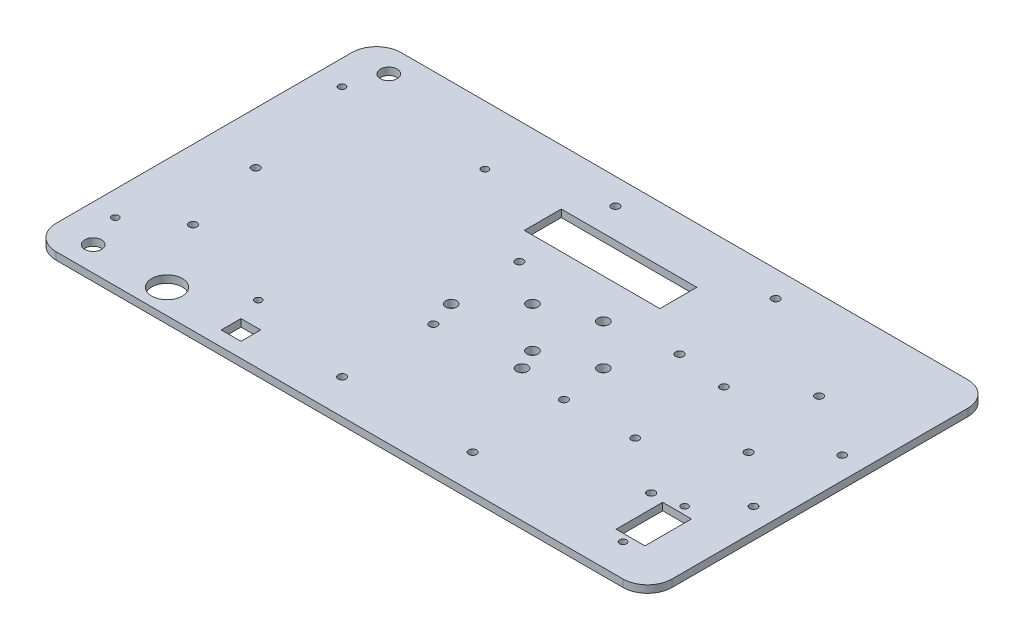
SolidWorks part; units mm, degrees
ref_plane "Front Plane" through (0, 0, 0) normal (0, 0, 1) x (1, 0, 0)
ref_plane "Top Plane" through (0, 0, 0) normal (0, 1, 0) x (1, 0, 0)
ref_plane "Right Plane" through (0, 0, 0) normal (1, 0, 0) x (0, 0, -1)
sketch "Sketch1" plane through (0, 0, 0) normal (0, 1, 0) x (1, 0, 0)
  line L1 (125, -70) -> (-125, -70)
  line L2 (125, -70) -> (125, 70)
  line L3 (125, 70) -> (-125, 70)
  line L4 (-125, -70) -> (-125, 70)
  line L5 (125, -70) -> (-125, 70) construction
  line L6 (125, 70) -> (-125, -70) construction
  point P0 (0, 0)
extrude "Boss-Extrude1" add sketch "Sketch1" along normal blind 3 contours L3 L4 L1 L2
fillet "Fillet2" radius 10 4 edges at (-125, 1.5, 70) (125, 1.5, 70) (-125, 1.5, -70) (125, 1.5, -70)
sketch "Sketch2" plane through (0, 0, 0) normal (0, 1, 0) x (1, 0, 0)
  line L0 (-125, 0) -> (125, 0)
  line L1 (-125, -60) -> (-125, 60) construction
  line L2 (125, -60) -> (125, 60) construction
  line L3 (116, -18) -> (116, 18)
  line L4 (-115, -46) -> (-115, 46)
  line L5 (116, 18) -> (68, 18)
  line L6 (116, 18) -> (116, -18)
  line L7 (116, -18) -> (68, -18)
  line L8 (68, 18) -> (68, -18)
  line L14 (0, 0.0606) -> (0, -55.9394)
  line L15 (37, -16.4394) -> (37, 16.5606)
  line L17 (96, 0) -> (-104, 0)
  line L18 (0, 0.0606) -> (37, 0.0606)
  line L20 (0, -55.9394) -> (-13, -55.9394)
  line L22 (0, -55.9394) -> (40, -55.9394)
  line L23 (-13, -55.9394) -> (-13, -18.9394)
  line L24 (37, 16.5606) -> (20.5, 16.5606)
  line L25 (-13, -18.9394) -> (40, -18.9394)
  line L26 (-13, -18.9394) -> (-13, -55.9394)
  line L27 (-13, -55.9394) -> (40, -55.9394)
  line L28 (40, -18.9394) -> (40, -55.9394)
  line L29 (37, 16.5606) -> (37, -16.4394)
  line L30 (37, -16.4394) -> (20.5, -16.4394)
  line L31 (20.5, 16.5606) -> (20.5, -16.4394)
  line L32 (0, -8.1894) -> (0, 8.3106)
  line L33 (16.5, 8.3106) -> (-16.5, 8.3106)
  line L34 (-115, 46) -> (-57, 46)
  line L35 (-115, 46) -> (-115, -46)
  line L36 (-115, -46) -> (-57, -46)
  line L37 (-57, 46) -> (-57, -46)
  line L38 (-125, 0) -> (-120.8393, 0)
  line L39 (16.5, -8.1894) -> (-16.5, -8.1894)
  line L40 (16.5, -8.1894) -> (16.5, 8.3106)
  line L41 (16.5, 8.3106) -> (-16.5, 8.3106)
  line L42 (-16.5, -8.1894) -> (-16.5, 8.3106)
  line L43 (16.5, -8.1894) -> (-16.5, 8.3106) construction
  line L44 (16.5, 8.3106) -> (-16.5, -8.1894) construction
  circle A0 centre (116, 18) radius 1.55
  circle A1 centre (68, 18) radius 1.55
  circle A2 centre (68, -18) radius 1.55
  circle A3 centre (116, -18) radius 1.55
  circle A8 centre (-13, -18.9394) radius 1.6
  circle A9 centre (-13, -55.9394) radius 1.6
  circle A10 centre (40, -18.9394) radius 1.6
  circle A11 centre (40, -55.9394) radius 1.6
  circle A12 centre (37, 0.0606) radius 2.25
  circle A13 centre (20.5, 16.5606) radius 2.25
  circle A14 centre (20.5, -16.4394) radius 2.25
  circle A15 centre (96, 0) radius 1.6
  circle A16 centre (-104, 0) radius 1.6
  circle A17 centre (-115, 46) radius 1.4
  circle A18 centre (-57, 46) radius 1.4
  circle A19 centre (-57, -46) radius 1.4
  circle A20 centre (-115, -46) radius 1.4
  circle A21 centre (-16.5, -8.1894) radius 2.25
  circle A22 centre (16.5, -8.1894) radius 2.25
  circle A23 centre (0, 8.3106) radius 2.25
  point P6 (116, 0)
  point P10 (116, 0)
  point P16 (0, 0)
  point P20 (-95, 0)
  point P25 (-115, 0)
  point P26 (68, 0)
  point P41 (37, 0.0606)
  point P46 (96, 0)
  point P55 (0, 0.0606)
  point P58 (0, 8.3106)
  point P67 (-120.8393, 0)
  point P69 (-104, 0)
  dimension "D1" = 200
  dimension "D2" = 53
  dimension "D3" = 37
  dimension "D4" = 36
  dimension "D5" = 48
  dimension "D6" = 16.5
  dimension "D7" = 33
sketch "Sketch3" plane through (0, 0, 0) normal (0, 1, 0) x (1, 0, 0)
  line L1 (115, -70) -> (-115, -70) construction
  line L2 (-125, -60) -> (-125, 60) construction
  circle A3 centre (-104, 0) radius 33.5
  circle A4 centre (96, 0) radius 195.5
  circle A5 centre (-96.745, -32.705) radius 1.6
  point P6 (-338.6726, 198.929)
  point P7 (-96.745, -32.705)
  dimension "D1" = 37.295
  dimension "D2" = 28.255
sketch "Sketch4" plane through (0, 3, 0) normal (0, 1, 0) x (1, 0, 0)
  line L2 (115, -70) -> (-115, -70) construction
  line L3 (125, -60) -> (125, 60) construction
  line L4 (115, 70) -> (-115, 70) construction
  circle A4 centre (96, 0) radius 34.5
  circle A5 centre (-104, 0) radius 197.5
  circle A6 centre (90.54, -34.0652) radius 1.6
  circle A7 centre (90.54, 34.0652) radius 1.6
  point P4 (90.54, 34.0652)
  point P5 (90.54, 34.0652)
  point P6 (90.54, 34.0652)
  point P7 (96, 0)
  point P8 (90.54, 34.0652)
  point P9 (-104, 0)
  point P10 (90.54, 34.0652)
  point P11 (90.54, 34.0652)
  point P13 (90.54, -34.0652)
  dimension "D1" = 35.9348
  dimension "D2" = 34.46
  dimension "D3" = 34.46
  dimension "D4" = 35.9348
sketch "Sketch5" plane through (0, 3, 0) normal (0, 1, 0) x (1, 0, 0)
  line L0 (110, -24) -> (110, -58)
  line L1 (94, -44.446) -> (110, -44.446)
  line L2 (110, -58) -> (94, -58)
  line L3 (110, -58) -> (110, -30.892)
  line L4 (110, -30.892) -> (94, -30.892)
  line L5 (94, -58) -> (94, -30.892)
  line L6 (102, -31.946) -> (102, -56.946)
  line L7 (-125, -60) -> (-80, -60)
  line L8 (107.85, -53.896) -> (96.15, -53.896)
  line L9 (107.85, -53.896) -> (107.85, -34.996)
  line L10 (107.85, -34.996) -> (96.15, -34.996)
  line L11 (96.15, -53.896) -> (96.15, -34.996)
  line L12 (107.85, -53.896) -> (96.15, -34.996) construction
  line L13 (107.85, -34.996) -> (96.15, -53.896) construction
  line L14 (0, 70) -> (0, 40)
  line L15 (115, 70) -> (-115, 70) construction
  line L16 (-80, -60) -> (-50, -60)
  line L17 (-27.5, 47.5) -> (27.5, 47.5)
  line L18 (-27.5, 47.5) -> (-27.5, 32.5)
  line L19 (-27.5, 32.5) -> (27.5, 32.5)
  line L20 (27.5, 47.5) -> (27.5, 32.5)
  line L21 (-27.5, 47.5) -> (27.5, 32.5) construction
  line L22 (-27.5, 32.5) -> (27.5, 47.5) construction
  line L23 (0, 0) -> (-125, 0)
  line L29 (-125, -60) -> (-125, 60) construction
  line L30 (-54, -56) -> (-46, -56)
  line L31 (-54, -56) -> (-54, -64)
  line L32 (-54, -64) -> (-46, -64)
  line L33 (-46, -56) -> (-46, -64)
  line L34 (-54, -56) -> (-46, -64) construction
  line L35 (-54, -64) -> (-46, -56) construction
  line L36 (-110, 60) -> (-110, -60)
  circle A0 centre (102, -31.946) radius 1.4
  circle A1 centre (102, -56.946) radius 1.4
  circle A2 centre (-110, -60) radius 3.4
  circle A3 centre (-80, -60) radius 6.2
  circle A5 centre (-110, 60) radius 3.4
  point P11 (102, -44.446)
  point P13 (102, -44.446)
  point P34 (-110, -60)
  point P46 (-110, 0)
extrude "Cut-Extrude5" cut sketch "Sketch2" against normal blind 7 and the other way blind 7 contours A17 | A18 | A20 | A19 | A16 | A23 | A21 | A22 | A13 | A12 | A10 | A14 | A8 | A9 | A11 | A1 | A0 | A15 | A3 | A2
extrude "Cut-Extrude6" cut sketch "Sketch3" against normal blind 7 and the other way blind 7 contours A5
extrude "Cut-Extrude7" cut sketch "Sketch4" against normal blind 7 and the other way blind 7 contours A7 | A6
extrude "Cut-Extrude8" cut sketch "Sketch5" against normal blind 7 and the other way blind 7 contours L20 L17 L18 L19 | A3 | L30 L33 L32 L31 | A0 | A1 | L10 L11 L8 L9 | A5 | A2 region at (-13.75, 3, -46.9299)
sketch "Sketch6" plane through (0, 3, 0) normal (0, 1, 0) x (1, 0, 0)
  line L0 (27.5, 20.5) -> (27.5, 59.5)
  line L1 (27.5, 59.5) -> (47.5, 59.5)
  line L2 (27.5, 20.5) -> (-17.5, 20.5)
  line L4 (-17.5, 20.5) -> (47.5, 20.5)
  line L5 (-17.5, 20.5) -> (-17.5, 59.5)
  line L6 (-17.5, 59.5) -> (47.5, 59.5)
  line L7 (47.5, 20.5) -> (47.5, 59.5)
  circle A0 centre (-17.5, 59.5) radius 1.6
  circle A1 centre (47.5, 59.5) radius 1.6
  circle A2 centre (-17.5, 20.5) radius 1.6
  circle A3 centre (47.5, 20.5) radius 1.6
  point P3 (27.5, 40)
extrude "Cut-Extrude9" cut sketch "Sketch6" against normal through all both and the other way through all contours A0 | A1 | A3 | A2
